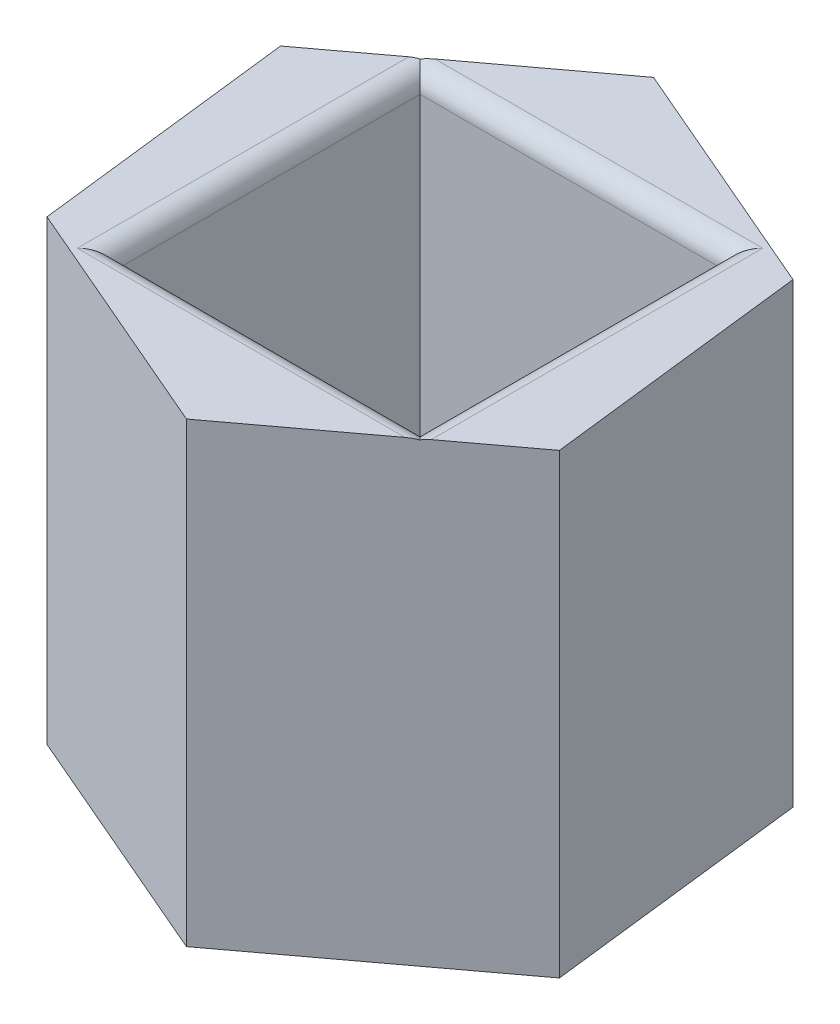
SolidWorks part; units mm, degrees
ref_plane "Front Plane" through (0, 0, 0) normal (0, 0, 1) x (1, 0, 0)
ref_plane "Top Plane" through (0, 0, 0) normal (0, 1, 0) x (1, 0, 0)
ref_plane "Right Plane" through (0, 0, 0) normal (1, 0, 0) x (0, 0, -1)
sketch "Sketch1" plane through (0, 0, 0) normal (0, 1, 0) x (1, 0, 0)
  line L1 (3.2148, -1.3838) -> (2.8058, 2.0922)
  line L2 (2.8058, 2.0922) -> (-0.409, 3.476)
  line L3 (-0.409, 3.476) -> (-3.2148, 1.3838)
  line L4 (-3.2148, 1.3838) -> (-2.8058, -2.0922)
  line L5 (-2.8058, -2.0922) -> (0.409, -3.476)
  line L6 (0.409, -3.476) -> (3.2148, -1.3838)
  circle A0 centre (0, 0) radius 3.0311 construction
  dimension "D1" = 7
extrude "Boss-Extrude1" add sketch "Sketch1" along normal blind 6
sketch "Sketch2" plane through (0, 6, 0) normal (0, 1, 0) x (1, 0, 0)
  line L1 (-2, -2) -> (2, -2)
  line L2 (-2, -2) -> (-2, 2)
  line L3 (-2, 2) -> (2, 2)
  line L4 (2, -2) -> (2, 2)
  line L5 (-2, -2) -> (2, 2) construction
  line L6 (-2, 2) -> (2, -2) construction
  circle A0 centre (0, 0) radius 1.95
  dimension "D1" = 3.9
  dimension "D2" = 4
  dimension "D3" = 4
extrude "Cut-Extrude1" cut sketch "Sketch2" against normal blind 5 contours L1 L4 L3 L2 A0 | A0 region at (-1.9943, 6, 0)
fillet "Fillet1" radius 0.25 4 edges at (0, 6, 2) (2, 6, 0) (0, 6, -2) (-2, 6, 0)
